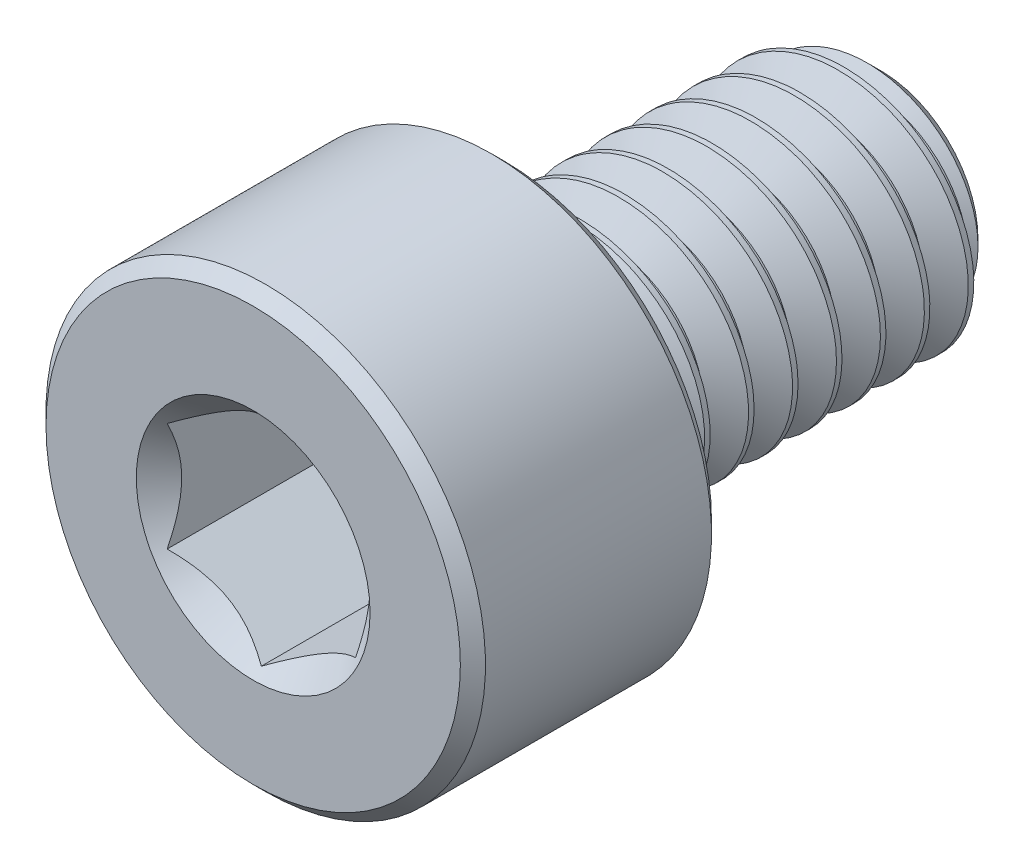
SolidWorks part; units mm, degrees
ref_plane "Front Plane" through (0, 0, 0) normal (0, 0, 1) x (1, 0, 0)
ref_plane "Top Plane" through (0, 0, 0) normal (0, 1, 0) x (1, 0, 0)
ref_plane "Right Plane" through (0, 0, 0) normal (1, 0, 0) x (0, 0, -1)
sketch "Sketch1" plane through (0, 0, 0) normal (1, 0, 0) x (0, 0, -1)
  line L0 (-5, 0) -> (5, 0) construction
  line L1 (5, 0) -> (5, 1.5453) construction
  line L2 (5, 1.5453) -> (4.5453, 2) construction
  line L3 (4.5453, 2) -> (4.475, 2) construction
  line L4 (4.475, 2) -> (-1, 2) construction
  line L5 (-1, 2) -> (-1, 3.5) construction
  line L6 (-1, 3.5) -> (-5, 3.5) construction
  line L7 (-5, 3.5) -> (-5, 0) construction
  line L8 (5, 1.5453) -> (5, 2) construction
  line L9 (4.9562, 2.0758) -> (5.3062, 1.4696) construction
  line L10 (5.3062, 1.4696) -> (5.6562, 2.0758) construction
  line L11 (5.6562, 2.0758) -> (4.9562, 2.0758) construction
  line L12 (5.3062, 2.0758) -> (5.3063, 2) construction
  line L13 (5.3062, 1.4696) -> (5.3062, 1.5453) construction
  line L14 (5.2625, 1.5453) -> (5.35, 1.5453) construction
  line L15 (5, 2) -> (5.6125, 2) construction
  line L16 (4.9781, 2.0379) -> (5.6344, 2.0379) construction
  line L17 (5, 0) -> (5, -2) construction
  line L18 (-1.2, 3.5) -> (-1, 3.3) construction
  line L19 (-4.8, 3.5) -> (-5, 3.3) construction
  line L20 (-1, 2) -> (-1, 0) construction
  line L21 (-1, 1) -> (1, 1) construction
  line L22 (1, 1) -> (3, 1) construction
  line L23 (3, 1) -> (5, 1) construction
  line L24 (1, 1) -> (1, 2) construction
  line L25 (1, 2) -> (1, 3.5) construction
  line L26 (3, 1) -> (3, 3.5) construction
  point P0 (-5, 1.5)
  point P3 (3.25, 2)
  point P4 (0, 0)
  point P18 (3, 2)
  point P22 (5.3062, 1.5453)
  point P24 (4.475, 2)
  point P25 (5.3063, 2)
  point P28 (5.3062, 2.0379)
  point P29 (3.25, -2)
  point P30 (1, 2)
  point P31 (-3, 3.5)
  point P37 (-1.7, 3.5)
  point P38 (-4.7, 3.5)
  point P45 (1, 1)
  point P46 (3, 1)
  dimension "D2" = 0.0875
  dimension "D7" = 0.2
  dimension "D8" = 0.2
  dimension "D9" = 0.2
  dimension "D10" = 0.1
  dimension "D11" = 0.5
  dimension "Drive Size" = 3
  dimension "Head Diameter" = 7
  dimension "Head Height" = 4
  dimension "Thread Pitch" = 0.7
  dimension "Thread Dia" = 4
  dimension "Length" = 6
  dimension "D12" = 0.525
  dimension "D4" = 1.75
  dimension "D3" = 45
sketch "Sketch2" plane through (0, 0, 0) normal (1, 0, 0) x (0, 0, -1)
  line L0 (-5, 0) -> (-5, 3.3)
  line L1 (-4.8, 3.5) -> (-1.2, 3.5)
  line L2 (-1, 3.3) -> (-1, 2.2)
  line L4 (4.5453, 2) -> (5, 1.5453)
  line L5 (5, 1.5453) -> (5, 0)
  line L6 (-1, 3.5) -> (-5, 3.5) construction
  line L7 (5, 0) -> (-5, 0)
  line L8 (-4.8, 3.5) -> (-5, 3.3) construction
  line L10 (-4.8, 3.5) -> (-5, 3.3)
  line L14 (-1.2, 3.5) -> (-1, 3.3) construction
  line L16 (-1.2, 3.5) -> (-1, 3.3)
  line L17 (-1, 2) -> (-1, 3.5) construction
  line L19 (-0.8, 2) -> (4.5453, 2)
  line L20 (4.475, 2) -> (-1, 2) construction
  arc A1 (-1, 2.2) -> (-0.8, 2) centre (-0.8, 2.2) ccw
  dimension "D3" = 0.2
revolve "Revolve1" add sketch "Sketch2" angle 360 about L7
sketch "Sketch3" plane through (0, 0, 5) normal (0, 0, 1) x (1, 0, 0)
  line L1 (1.5, -0.866) -> (1.5, 0.866)
  line L2 (1.5, 0.866) -> (0, 1.7321)
  line L3 (0, 1.7321) -> (-1.5, 0.866)
  line L4 (-1.5, 0.866) -> (-1.5, -0.866)
  line L5 (-1.5, -0.866) -> (0, -1.7321)
  line L6 (0, -1.7321) -> (1.5, -0.866)
  circle A0 centre (0, 0) radius 1.5 construction
  circle A1 centre (0, 0) radius 3.5 construction
  circle A2 centre (0, 0) radius 3.5 construction
  circle A3 centre (0, 0) radius 1.7321 construction
  point P13 (0, 0)
  dimension "D1" = 3.4641
extrude "Cut-Extrude1" cut sketch "Sketch3" against normal offset from surface (3 mm away) 1 up to face at (0, 3.3, 1)
sketch "Sketch4" plane through (0, 0, 5) normal (0, 0, 1) x (1, 0, 0)
  circle A0 centre (0, 0) radius 1.862
  dimension "D1" = 3.7239
extrude "Cut-Extrude2" cut sketch "Sketch4" against normal up to vertex (2 mm away) draft 45 up to point (0, 3.5, 3)
sketch "Sketch11" plane through (0, 0, 0) normal (1, 0, 0) x (0, 0, -1)
  line L0 (-5, 0) -> (5, 0) construction
  line L1 (-5, 0) -> (5, 0) construction
  line L2 (0.125, 0) -> (0.125, 2) construction
  line L3 (4.475, 2) -> (-1, 2) construction
  line L4 (3.875, 0) -> (3.875, 2) construction
  line L6 (5, 1.5453) -> (5, 2) construction
  point P2 (0.125, 0)
  point P3 (3.875, 0)
  dimension "D1" = 1.125
  dimension "D2" = 1.125
sketch "Sketch6" plane through (0, 0, -5) normal (0, 0, -1) x (-1, 0, 0)
  circle A0 centre (0, 0) radius 2
curve "Helix/Spiral1" pitch 0.7 height 6.7 turns 9.5714
sketch "Sketch10" plane through (0, 0, 0) normal (1, 0, 0) x (0, 0, -1)
  line L0 (-0.8, -3.5) -> (-0.8, 3.5)
  line L5 (-5, 0) -> (5, 0) construction
  line L6 (-0.8, 2) -> (-0.8, -2) construction
  point P3 (-0.8, 0)
split "Split1" trim tools "Sketch10" bodies to split 106 resulting bodies 114 115
sketch "Sketch7" plane through (0, 0, 0) normal (1, 0, 0) x (0, 0, -1)
  line L0 (4.9781, 2.0379) -> (5.6344, 2.0379)
  line L1 (5.6344, 2.0379) -> (5.35, 1.5453)
  line L2 (5.35, 1.5453) -> (5.2625, 1.5453)
  line L3 (5.2625, 1.5453) -> (4.9781, 2.0379)
sweep "Cut-Sweep1" cut profiles "Sketch7" path "Helix/Spiral1" align with end faces yes
sketch "Sketch8" plane through (0, 0, 0) normal (1, 0, 0) x (0, 0, -1)
  line L0 (-1, 0) -> (-1, 2)
  line L1 (-0.8, -2) -> (-0.8, 2) construction
  line L2 (-1, 2) -> (-0.8, 2)
  line L4 (-0.8, 2) -> (0.3547, 0)
  line L5 (0.3547, 0) -> (-1, 0)
  line L6 (4.475, 2) -> (-1, 2) construction
  line L7 (-5, 0) -> (5, 0) construction
  dimension "D1" = 60
revolve "Revolve2" add sketch "Sketch8" angle 360 about L5
equation "\"D2@Sketch1\" = \"Thread Pitch@Sketch1\" / 8"
equation "\"D4@Helix/Spiral1\" = \"Thread Pitch@Sketch1\""
equation "\"D7@Sketch1\" = \"Head Height@Sketch1\" * .05"
equation "\"D8@Sketch1\"=\"D7@Sketch1\""
equation "\"D9@Sketch1\"=\"D7@Sketch1\""
equation "\"D10@Sketch1\"=\"D7@Sketch1\"/2"
equation "\"D11@Sketch1\"=\"D10@Sketch1\"*5"
equation "\"D4@Sketch1\"=\"Thread Pitch@Sketch1\"*2.5"
equation "\"D12@Sketch1\"=\"Thread Pitch@Sketch1\"*.75"
equation "\"D3@Helix/Spiral1\"=\"Length@Sketch1\"+\"Thread Pitch@Sketch1\""
equation "\"D3@Sketch2\"=\"Thread Dia@Sketch1\"*0.05"
equation "\"D1@Sketch11\"=\"Length@Sketch1\"*0.1875"
equation "\"D2@Sketch11\"=\"D1@Sketch11\""
equation "\"D1@Sketch4\"=\"D1@Sketch3\"*1.075"
